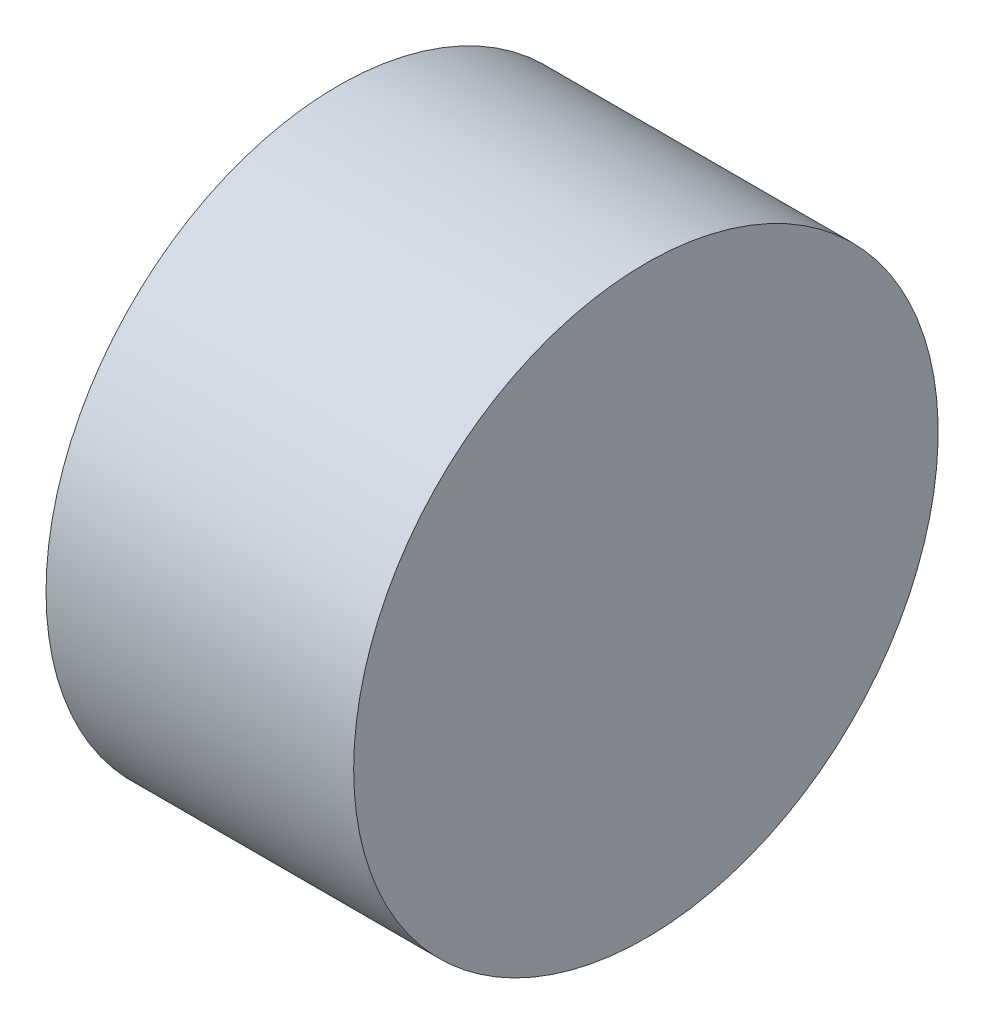
SolidWorks part; units mm, degrees
ref_plane "Face" through (0, 0, 0) normal (0, 0, 1) x (1, 0, 0)
ref_plane "Dessus" through (0, 0, 0) normal (0, 1, 0) x (1, 0, 0)
ref_plane "Droite" through (0, 0, 0) normal (1, 0, 0) x (0, 0, -1)
sketch "Esquisse1" plane through (0, 0, 0) normal (0, 0, 1) x (1, 0, 0)
  line L0 (0, 0) -> (0, 4.75)
  line L1 (0, 4.75) -> (-5, 4.75)
  line L2 (-5, 4.75) -> (-5, 4)
  line L3 (-5, 4) -> (-0.75, 4)
  line L4 (-0.75, 4) -> (-0.75, 0)
  line L5 (0, 0) -> (-0.75, 0)
  line L6 (-124.153, 0) -> (93.8513, 0) construction
  dimension "D1" = 0.75
  dimension "D2" = 4
  dimension "D3" = 4.75
  dimension "D4" = 5
revolve "Base-Révolution" add sketch "Esquisse1" angle 360 about L6
sketch "Esquisse2" plane through (-5, 0, 0) normal (-1, 0, 0) x (0, 0, 1)
  line L0 (0, 0) -> (0, 5.5772) construction
  line L3 (-0.25, 4.7434) -> (0, 4.6)
  line L4 (0.25, 4.7434) -> (0, 4.6)
  circle A0 centre (0, 0) radius 4.75 construction
  arc A1 (0.25, 4.7434) -> (-0.25, 4.7434) centre (0, 0) ccw
  dimension "D2" = 4.6
  dimension "D1" = 0.5
ref_axis "Axe1" through (0, 0, 0) along (-1, 0, 0)
